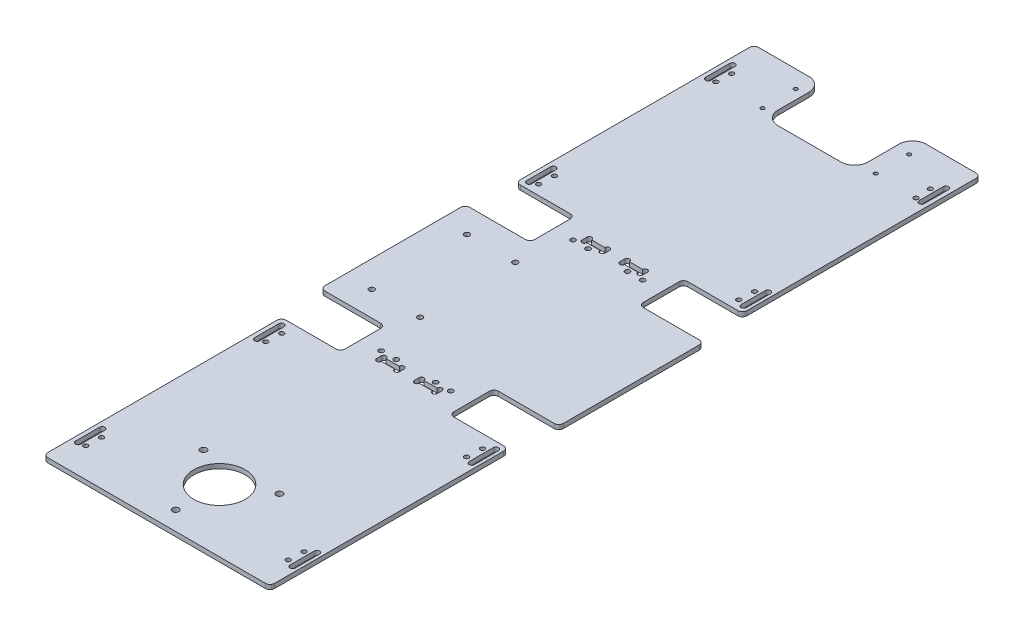
SolidWorks part; units mm, degrees
material "Thornel Mat VMA"
ref_plane "前视基准面" through (0, 0, 0) normal (0, 0, 1) x (1, 0, 0)
ref_plane "上视基准面" through (0, 0, 0) normal (0, 1, 0) x (1, 0, 0)
ref_plane "右视基准面" through (0, 0, 0) normal (1, 0, 0) x (0, 0, -1)
other "Configuration Table"
sketch "草图1" plane through (0, 0, 0) normal (0, 1, 0) x (1, 0, 0)
  line L0 (30.075, -69.59) -> (30.075, -66.41)
  line L1 (22.5, -69.59) -> (22.5, -66.41) construction
  line L7 (30.075, -68) -> (14.925, -68) construction
  line L8 (26.875, -69.59) -> (18.125, -69.59)
  line L9 (26.875, -66.41) -> (18.125, -66.41)
  line L14 (43.125, 69.59) -> (51.875, 69.59)
  line L15 (39.925, 69.59) -> (39.925, 66.41)
  line L16 (43.125, 66.41) -> (51.875, 66.41)
  line L17 (55.075, 69.59) -> (55.075, 66.41)
  line L18 (55.075, -69.59) -> (55.075, -66.41)
  line L19 (43.125, -66.41) -> (51.875, -66.41)
  line L20 (39.925, -69.59) -> (39.925, -66.41)
  line L21 (43.125, -69.59) -> (51.875, -69.59)
  line L22 (47.5, 69.59) -> (47.5, 66.41) construction
  line L23 (39.925, 68) -> (55.075, 68) construction
  line L24 (39.925, -68) -> (55.075, -68) construction
  line L25 (47.5, -69.59) -> (47.5, -66.41) construction
  line L27 (14.925, -69.59) -> (14.925, -66.41)
  line L29 (-1, -77.5) -> (-40, -77.5)
  line L30 (30.075, 68) -> (14.925, 68) construction
  line L31 (22.5, 69.59) -> (22.5, 66.41) construction
  line L33 (-1, 77.5) -> (-40, 77.5)
  line L54 (71, 77.5) -> (110, 77.5)
  line L56 (35, 153.4687) -> (35, -164.7089) construction
  line L58 (71, -77.5) -> (110, -77.5)
  line L64 (110, 235.15) -> (110, 77.5)
  line L67 (14.925, 69.59) -> (14.925, 66.41)
  line L68 (26.875, 66.41) -> (18.125, 66.41)
  line L69 (26.875, 69.59) -> (18.125, 69.59)
  line L70 (30.075, 69.59) -> (30.075, 66.41)
  line L72 (-40, 235.15) -> (110, 235.15)
  line L74 (-40, -235.15) -> (110, -235.15)
  line L77 (71, 77.5) -> (71, 47.9372)
  line L78 (-1, 77.5) -> (-1, 47.9372)
  line L84 (-40, 235.15) -> (-40, 77.5)
  line L85 (-1, 47.9372) -> (-43.8991, 47.9372)
  line L86 (-43.8991, 47.9372) -> (-43.8991, -47.9372)
  line L90 (113.8991, 47.9372) -> (113.8991, -47.9372)
  line L91 (71, 47.9372) -> (113.8991, 47.9372)
  line L93 (71, -47.9372) -> (113.8991, -47.9372)
  line L94 (-1, -47.9372) -> (-43.8991, -47.9372)
  line L95 (110, -77.5) -> (110, -235.15)
  line L96 (-1, -47.9372) -> (-1, -77.5)
  line L97 (71, -47.9372) -> (71, -77.5)
  line L98 (-40, -77.5) -> (-40, -235.15)
  arc A8 (39.925, 69.59) -> (43.125, 69.59) centre (41.525, 69.59) cw
  arc A9 (55.075, 69.59) -> (51.875, 69.59) centre (53.475, 69.59) ccw
  arc A10 (55.075, 66.41) -> (51.875, 66.41) centre (53.475, 66.41) cw
  arc A11 (39.925, 66.41) -> (43.125, 66.41) centre (41.525, 66.41) ccw
  arc A12 (39.925, -66.41) -> (43.125, -66.41) centre (41.525, -66.41) cw
  arc A13 (55.075, -66.41) -> (51.875, -66.41) centre (53.475, -66.41) ccw
  arc A14 (55.075, -69.59) -> (51.875, -69.59) centre (53.475, -69.59) cw
  arc A15 (39.925, -69.59) -> (43.125, -69.59) centre (41.525, -69.59) ccw
  circle A50 centre (48.025, -63.59) radius 1.6
  circle A51 centre (58.025, -63.59) radius 1.6
  circle A52 centre (58.025, 63.41) radius 1.6
  circle A53 centre (48.025, 63.41) radius 1.6
  arc A54 (30.075, -69.59) -> (26.875, -69.59) centre (28.475, -69.59) cw
  arc A55 (30.075, -66.41) -> (26.875, -66.41) centre (28.475, -66.41) ccw
  circle A56 centre (11.975, -63.59) radius 1.6
  circle A57 centre (21.975, -63.59) radius 1.6
  arc A58 (14.925, -69.59) -> (18.125, -69.59) centre (16.525, -69.59) ccw
  arc A59 (14.925, -66.41) -> (18.125, -66.41) centre (16.525, -66.41) cw
  circle A60 centre (21.975, 63.41) radius 1.6
  circle A61 centre (11.975, 63.41) radius 1.6
  arc A62 (30.075, 66.41) -> (26.875, 66.41) centre (28.475, 66.41) cw
  arc A63 (14.925, 66.41) -> (18.125, 66.41) centre (16.525, 66.41) ccw
  arc A64 (14.925, 69.59) -> (18.125, 69.59) centre (16.525, 69.59) cw
  arc A65 (30.075, 69.59) -> (26.875, 69.59) centre (28.475, 69.59) ccw
  point P28 (35, -97.5)
  point P79 (35, 97.5)
  point P141 (64, 0)
  point P146 (-64, 0)
  dimension "D12" = 4.925
extrude "凸台-拉伸1" add sketch "草图1" along normal blind 3
fillet "圆角1" radius 3 20 edges at (-40, 1.5, -235.15) (110, 1.5, -235.15) (113.8991, 1.5, -47.9372) (110, 1.5, -77.5) (71, 1.5, -77.5) (71, 1.5, -47.9372) (-40, 1.5, -77.5) (-1, 1.5, -77.5) (-1, 1.5, -47.9372) (-43.8991, 1.5, -47.9372) (-43.8991, 1.5, 47.9372) (-1, 1.5, 47.9372) (113.8991, 1.5, 47.9372) (71, 1.5, 47.9372) (-40, 1.5, 77.5) (-1, 1.5, 77.5) (71, 1.5, 77.5) (110, 1.5, 77.5) (110, 1.5, 235.15) (-40, 1.5, 235.15)
sketch "草图2" plane through (0, 3, 0) normal (0, 1, 0) x (1, 0, 0)
  line L0 (107.85, 215.4743) -> (104.85, 215.4743) construction
  line L1 (107.85, 216.4743) -> (104.85, 216.4743)
  line L2 (107.85, 216.4743) -> (107.85, 200.4743)
  line L3 (107.85, 200.4743) -> (104.85, 200.4743)
  line L4 (104.85, 216.4743) -> (104.85, 200.4743)
  line L5 (107.85, 98) -> (104.85, 98)
  line L6 (107.85, 98) -> (107.85, 82)
  line L7 (107.85, 82) -> (104.85, 82)
  line L8 (104.85, 98) -> (104.85, 82)
  line L9 (-34.15, 216.4743) -> (-37.15, 216.4743)
  line L10 (-34.15, 216.4743) -> (-34.15, 200.4743)
  line L11 (-34.15, 200.4743) -> (-37.15, 200.4743)
  line L12 (-37.15, 216.4743) -> (-37.15, 200.4743)
  line L13 (-34.15, 98) -> (-37.15, 98)
  line L14 (-34.15, 98) -> (-34.15, 82)
  line L15 (-34.15, 82) -> (-37.15, 82)
  line L16 (-37.15, 98) -> (-37.15, 82)
  line L17 (107.85, 214.4743) -> (104.85, 214.4743)
  line L18 (107.85, 216.4743) -> (104.85, 216.4743)
  line L19 (107.85, 201.4743) -> (104.85, 201.4743) construction
  line L20 (107.85, 200.4743) -> (104.85, 200.4743)
  line L21 (107.85, 202.4743) -> (104.85, 202.4743)
  line L22 (107.85, 97) -> (104.85, 97) construction
  line L23 (107.85, 96) -> (104.85, 96)
  line L24 (107.85, 98) -> (104.85, 98)
  line L25 (107.85, 83) -> (104.85, 83) construction
  line L26 (107.85, 82) -> (104.85, 82)
  line L27 (107.85, 84) -> (104.85, 84)
  line L28 (-34.15, 215.4743) -> (-37.15, 215.4743) construction
  line L29 (-34.15, 214.4743) -> (-37.15, 214.4743)
  line L30 (-34.15, 216.4743) -> (-37.15, 216.4743)
  line L31 (-34.15, 201.4743) -> (-37.15, 201.4743) construction
  line L32 (-34.15, 200.4743) -> (-37.15, 200.4743)
  line L33 (-34.15, 202.4743) -> (-37.15, 202.4743)
  line L34 (-34.15, 97) -> (-37.15, 97) construction
  line L35 (-34.15, 96) -> (-37.15, 96)
  line L36 (-34.15, 98) -> (-37.15, 98)
  line L37 (-34.15, 83) -> (-37.15, 83) construction
  line L38 (-34.15, 82) -> (-37.15, 82)
  line L39 (-34.15, 84) -> (-37.15, 84)
  line L40 (107.85, 208.4743) -> (96.4125, 208.4743) construction
  line L41 (107.85, 90) -> (95.3231, 90) construction
  line L42 (-37.15, 90) -> (-24.8235, 90) construction
  line L43 (-37.15, 208.4743) -> (-26.5733, 208.4743) construction
  arc A0 (107.85, 214.4743) -> (107.85, 216.4743) centre (107.85, 215.4743) ccw
  arc A1 (104.85, 216.4743) -> (104.85, 214.4743) centre (104.85, 215.4743) ccw
  arc A2 (107.85, 200.4743) -> (107.85, 202.4743) centre (107.85, 201.4743) ccw
  arc A3 (104.85, 202.4743) -> (104.85, 200.4743) centre (104.85, 201.4743) ccw
  arc A4 (107.85, 96) -> (107.85, 98) centre (107.85, 97) ccw
  arc A5 (104.85, 98) -> (104.85, 96) centre (104.85, 97) ccw
  arc A6 (107.85, 82) -> (107.85, 84) centre (107.85, 83) ccw
  arc A7 (104.85, 84) -> (104.85, 82) centre (104.85, 83) ccw
  arc A8 (-34.15, 214.4743) -> (-34.15, 216.4743) centre (-34.15, 215.4743) ccw
  arc A9 (-37.15, 216.4743) -> (-37.15, 214.4743) centre (-37.15, 215.4743) ccw
  arc A10 (-34.15, 200.4743) -> (-34.15, 202.4743) centre (-34.15, 201.4743) ccw
  arc A11 (-37.15, 202.4743) -> (-37.15, 200.4743) centre (-37.15, 201.4743) ccw
  arc A12 (-34.15, 96) -> (-34.15, 98) centre (-34.15, 97) ccw
  arc A13 (-37.15, 98) -> (-37.15, 96) centre (-37.15, 97) ccw
  arc A14 (-34.15, 82) -> (-34.15, 84) centre (-34.15, 83) ccw
  arc A15 (-37.15, 84) -> (-37.15, 82) centre (-37.15, 83) ccw
  circle A16 centre (101.35, 203.4743) radius 1.5
  circle A17 centre (101.35, 213.4743) radius 1.5
  circle A18 centre (101.35, 85) radius 1.5
  circle A19 centre (101.35, 95) radius 1.5
  circle A20 centre (-30.65, 95) radius 1.5
  circle A21 centre (-30.65, 85) radius 1.5
  circle A22 centre (-30.65, 213.4743) radius 1.5
  circle A23 centre (-30.65, 203.4743) radius 1.5
  point P26 (106.35, 215.4743)
  point P31 (106.35, 201.4743)
  point P38 (106.35, 97)
  point P45 (106.35, 83)
  point P52 (-35.65, 215.4743)
  point P59 (-35.65, 201.4743)
  point P66 (-35.65, 97)
  point P73 (-35.65, 83)
  dimension "D1" = 1
  dimension "D2" = 1
  dimension "D3" = 1
  dimension "D4" = 1
  dimension "D5" = 1
  dimension "D6" = 1
  dimension "D7" = 1
  dimension "D8" = 1
  dimension "D9" = 3
  dimension "D14" = 3
  dimension "D15" = 3
  dimension "D18" = 3
  dimension "D10" = 3.5
  dimension "D11" = 5
  dimension "D12" = 3.5
  dimension "D13" = 5
  dimension "D16" = 3.5
  dimension "D17" = 5
  dimension "D19" = 5
  dimension "D20" = 3.5
sketch "草图3" plane through (0, 3, 0) normal (0, 1, 0) x (1, 0, 0)
  line L2 (104.85, 214.4743) -> (107.85, 214.4743)
  line L3 (107.85, 216.4743) -> (104.85, 216.4743)
  line L4 (-34.15, 216.4743) -> (-37.15, 216.4743)
  line L5 (-37.15, 216.4743) -> (-37.15, 200.4743)
  line L6 (-37.15, 200.4743) -> (-34.15, 200.4743)
  line L7 (-34.15, 200.4743) -> (-34.15, 216.4743)
  line L8 (-34.15, 216.4743) -> (-37.15, 216.4743)
  line L9 (-37.15, 216.4743) -> (-37.15, 200.4743)
  line L10 (-37.15, 200.4743) -> (-34.15, 200.4743)
  line L11 (-34.15, 200.4743) -> (-34.15, 216.4743)
  line L12 (107.85, 98) -> (104.85, 98)
  line L13 (104.85, 98) -> (104.85, 82)
  line L14 (104.85, 82) -> (107.85, 82)
  line L15 (107.85, 82) -> (107.85, 98)
  line L16 (107.85, 98) -> (104.85, 98)
  line L17 (104.85, 98) -> (104.85, 82)
  line L18 (104.85, 82) -> (107.85, 82)
  line L19 (107.85, 82) -> (107.85, 98)
  line L20 (107.85, 216.4743) -> (104.85, 216.4743)
  line L21 (104.85, 216.4743) -> (104.85, 200.4743)
  line L22 (104.85, 200.4743) -> (107.85, 200.4743)
  line L23 (107.85, 200.4743) -> (107.85, 216.4743)
  line L24 (107.85, 216.4743) -> (104.85, 216.4743)
  line L25 (104.85, 216.4743) -> (104.85, 200.4743)
  line L26 (104.85, 200.4743) -> (107.85, 200.4743)
  line L27 (107.85, 200.4743) -> (107.85, 216.4743)
  line L28 (104.85, 214.4743) -> (107.85, 214.4743)
  line L29 (107.85, 216.4743) -> (104.85, 216.4743)
  line L30 (104.85, 96) -> (107.85, 96)
  line L31 (107.85, 98) -> (104.85, 98)
  line L32 (-34.15, 98) -> (-37.15, 98)
  line L33 (-37.15, 98) -> (-37.15, 82)
  line L34 (-37.15, 82) -> (-34.15, 82)
  line L35 (-34.15, 82) -> (-34.15, 98)
  line L36 (-34.15, 98) -> (-37.15, 98)
  line L37 (-37.15, 98) -> (-37.15, 82)
  line L38 (-37.15, 82) -> (-34.15, 82)
  line L39 (-34.15, 82) -> (-34.15, 98)
  line L40 (104.85, 96) -> (107.85, 96)
  line L41 (107.85, 98) -> (104.85, 98)
  line L42 (104.85, 200.4743) -> (107.85, 200.4743)
  line L43 (107.85, 202.4743) -> (104.85, 202.4743)
  line L44 (104.85, 200.4743) -> (107.85, 200.4743)
  line L45 (107.85, 202.4743) -> (104.85, 202.4743)
  line L46 (-37.15, 214.4743) -> (-34.15, 214.4743)
  line L47 (-34.15, 216.4743) -> (-37.15, 216.4743)
  line L48 (-37.15, 214.4743) -> (-34.15, 214.4743)
  line L49 (-34.15, 216.4743) -> (-37.15, 216.4743)
  line L50 (104.85, 82) -> (107.85, 82)
  line L51 (107.85, 84) -> (104.85, 84)
  line L52 (104.85, 82) -> (107.85, 82)
  line L53 (107.85, 84) -> (104.85, 84)
  line L54 (-37.15, 82) -> (-34.15, 82)
  line L55 (-34.15, 84) -> (-37.15, 84)
  line L56 (-37.15, 82) -> (-34.15, 82)
  line L57 (-34.15, 84) -> (-37.15, 84)
  line L58 (-37.15, 96) -> (-34.15, 96)
  line L59 (-34.15, 98) -> (-37.15, 98)
  line L60 (-37.15, 96) -> (-34.15, 96)
  line L61 (-34.15, 98) -> (-37.15, 98)
  line L67 (-37.15, -200.4743) -> (-34.15, -200.4743)
  line L68 (-35.15, -202.8885) -> (-37.15, -202.4743)
  line L69 (-34.15, -98) -> (-37.15, -98)
  line L70 (-37.15, -96) -> (-34.15, -96)
  line L71 (-34.15, -84) -> (-37.15, -84)
  line L72 (-37.15, -82) -> (-34.15, -82)
  line L73 (107.85, -84) -> (104.85, -84)
  line L74 (104.85, -82) -> (107.85, -82)
  line L75 (-34.15, -216.4743) -> (-37.15, -216.4743)
  line L76 (-37.15, -214.4743) -> (-34.15, -214.4743)
  line L77 (107.85, -202.4743) -> (104.85, -202.4743)
  line L78 (104.85, -200.4743) -> (107.85, -200.4743)
  line L79 (107.85, -98) -> (104.85, -98)
  line L80 (104.85, -96) -> (107.85, -96)
  line L81 (-34.15, -82) -> (-34.15, -98)
  line L82 (-37.15, -82) -> (-34.15, -82)
  line L83 (-37.15, -98) -> (-37.15, -82)
  line L84 (-34.15, -98) -> (-37.15, -98)
  line L85 (107.85, -216.4743) -> (104.85, -216.4743)
  line L86 (104.85, -214.4743) -> (107.85, -214.4743)
  line L87 (107.85, -200.4743) -> (107.85, -216.4743)
  line L88 (104.85, -200.4743) -> (107.85, -200.4743)
  line L89 (104.85, -216.4743) -> (104.85, -200.4743)
  line L90 (107.85, -216.4743) -> (104.85, -216.4743)
  line L91 (107.85, -82) -> (107.85, -98)
  line L92 (104.85, -82) -> (107.85, -82)
  line L93 (104.85, -98) -> (104.85, -82)
  line L94 (107.85, -98) -> (104.85, -98)
  line L95 (-34.15, -200.4743) -> (-34.15, -216.4743)
  line L96 (-37.15, -200.4743) -> (-34.15, -200.4743)
  line L97 (-37.15, -216.4743) -> (-37.15, -200.4743)
  line L98 (-34.15, -216.4743) -> (-37.15, -216.4743)
  line L99 (-35.65, 216.4743) -> (-35.65, 200.4743) construction
  line L100 (-33.8992, 216.4743) -> (-33.8992, 200.4743)
  line L101 (-37.4008, 216.4743) -> (-37.4008, 200.4743)
  line L104 (105.65, 216.4743) -> (105.65, 200.4743) construction
  line L105 (103.8992, 216.4743) -> (103.8992, 200.4743)
  line L106 (107.4008, 216.4743) -> (107.4008, 200.4743)
  circle A0 centre (-30.65, -85) radius 1.5
  circle A1 centre (-30.65, 95) radius 1.5
  arc A2 (104.85, 216.4743) -> (104.85, 214.4743) centre (104.85, 215.4743) ccw
  arc A3 (107.85, 214.4743) -> (107.85, 216.4743) centre (107.85, 215.4743) ccw
  arc A4 (104.85, 216.4743) -> (104.85, 214.4743) centre (104.85, 215.4743) ccw
  arc A5 (107.85, 214.4743) -> (107.85, 216.4743) centre (107.85, 215.4743) ccw
  arc A6 (104.85, 98) -> (104.85, 96) centre (104.85, 97) ccw
  arc A7 (107.85, 96) -> (107.85, 98) centre (107.85, 97) ccw
  arc A8 (104.85, 98) -> (104.85, 96) centre (104.85, 97) ccw
  arc A9 (107.85, 96) -> (107.85, 98) centre (107.85, 97) ccw
  arc A10 (104.85, 202.4743) -> (104.85, 200.4743) centre (104.85, 201.4743) ccw
  arc A11 (107.85, 200.4743) -> (107.85, 202.4743) centre (107.85, 201.4743) ccw
  arc A12 (104.85, 202.4743) -> (104.85, 200.4743) centre (104.85, 201.4743) ccw
  arc A13 (107.85, 200.4743) -> (107.85, 202.4743) centre (107.85, 201.4743) ccw
  arc A14 (-37.15, 216.4743) -> (-37.15, 214.4743) centre (-37.15, 215.4743) ccw
  arc A15 (-34.15, 214.4743) -> (-34.15, 216.4743) centre (-34.15, 215.4743) ccw
  arc A16 (-37.15, 216.4743) -> (-37.15, 214.4743) centre (-37.15, 215.4743) ccw
  arc A18 (104.85, 84) -> (104.85, 82) centre (104.85, 83) ccw
  arc A19 (107.85, 82) -> (107.85, 84) centre (107.85, 83) ccw
  arc A20 (104.85, 84) -> (104.85, 82) centre (104.85, 83) ccw
  arc A21 (107.85, 82) -> (107.85, 84) centre (107.85, 83) ccw
  arc A22 (-37.15, 84) -> (-37.15, 82) centre (-37.15, 83) ccw
  arc A23 (-34.15, 82) -> (-34.15, 84) centre (-34.15, 83) ccw
  arc A24 (-37.15, 84) -> (-37.15, 82) centre (-37.15, 83) ccw
  arc A25 (-34.15, 82) -> (-34.15, 84) centre (-34.15, 83) ccw
  arc A26 (-37.15, 98) -> (-37.15, 96) centre (-37.15, 97) ccw
  arc A27 (-34.15, 96) -> (-34.15, 98) centre (-34.15, 97) ccw
  arc A28 (-37.15, 98) -> (-37.15, 96) centre (-37.15, 97) ccw
  arc A29 (-34.15, 96) -> (-34.15, 98) centre (-34.15, 97) ccw
  circle A34 centre (-30.65, 95) radius 1.5
  circle A35 centre (101.35, 95) radius 1.5
  circle A36 centre (101.35, 95) radius 1.5
  circle A37 centre (101.35, 85) radius 1.5
  circle A38 centre (101.35, 85) radius 1.5
  circle A39 centre (101.35, 213.4743) radius 1.5
  circle A40 centre (101.35, 213.4743) radius 1.5
  circle A41 centre (101.35, 203.4743) radius 1.5
  circle A42 centre (101.35, 203.4743) radius 1.5
  circle A43 centre (-30.65, 203.4743) radius 1.5
  circle A44 centre (-30.65, 203.4743) radius 1.5
  circle A45 centre (-30.65, 213.4743) radius 1.5
  circle A46 centre (-30.65, 213.4743) radius 1.5
  circle A47 centre (-30.65, 85) radius 1.5
  circle A48 centre (-30.65, 85) radius 1.5
  circle A49 centre (-30.65, -213.4743) radius 1.5
  circle A50 centre (-30.65, -203.4743) radius 1.5
  circle A51 centre (101.35, -203.4743) radius 1.5
  circle A52 centre (101.35, -213.4743) radius 1.5
  circle A53 centre (101.35, -85) radius 1.5
  circle A54 centre (101.35, -95) radius 1.5
  circle A55 centre (-30.65, -95) radius 1.5
  arc A56 (-34.15, -200.4743) -> (-35.15, -202.8885) centre (-35.15, -201.4743) cw
  arc A57 (-37.15, -202.4743) -> (-37.15, -200.4743) centre (-37.15, -201.4743) cw
  arc A58 (-34.15, -96) -> (-34.15, -98) centre (-34.15, -97) cw
  arc A59 (-37.15, -98) -> (-37.15, -96) centre (-37.15, -97) cw
  arc A60 (-34.15, -82) -> (-34.15, -84) centre (-34.15, -83) cw
  arc A61 (-37.15, -84) -> (-37.15, -82) centre (-37.15, -83) cw
  arc A62 (107.85, -82) -> (107.85, -84) centre (107.85, -83) cw
  arc A63 (104.85, -84) -> (104.85, -82) centre (104.85, -83) cw
  arc A64 (-34.15, -214.4743) -> (-34.15, -216.4743) centre (-34.15, -215.4743) cw
  arc A65 (-37.15, -216.4743) -> (-37.15, -214.4743) centre (-37.15, -215.4743) cw
  arc A66 (107.85, -200.4743) -> (107.85, -202.4743) centre (107.85, -201.4743) cw
  arc A67 (104.85, -202.4743) -> (104.85, -200.4743) centre (104.85, -201.4743) cw
  arc A68 (107.85, -96) -> (107.85, -98) centre (107.85, -97) cw
  arc A69 (104.85, -98) -> (104.85, -96) centre (104.85, -97) cw
  arc A70 (107.85, -214.4743) -> (107.85, -216.4743) centre (107.85, -215.4743) cw
  arc A71 (104.85, -216.4743) -> (104.85, -214.4743) centre (104.85, -215.4743) cw
  arc A72 (-33.8992, 216.4743) -> (-37.4008, 216.4743) centre (-35.65, 216.4743) ccw
  arc A73 (-37.4008, 200.4743) -> (-33.8992, 200.4743) centre (-35.65, 200.4743) ccw
  arc A74 (103.8992, 216.4743) -> (107.4008, 216.4743) centre (105.65, 216.4743) cw
  arc A75 (107.4008, 200.4743) -> (103.8992, 200.4743) centre (105.65, 200.4743) cw
  point P61 (-35.65, 208.4743)
  point P165 (105.65, 208.4743)
  dimension "D12" = 3.5016
  dimension "D1" = 0
  dimension "D2" = 0
  dimension "D3" = 0
  dimension "D4" = 0
  dimension "D5" = 0
  dimension "D6" = 0
  dimension "D7" = 0
  dimension "D8" = 0
  dimension "D9" = 0
  dimension "D10" = 0
  dimension "D11" = 0
  dimension "D13" = 0
  dimension "D14" = 0
  dimension "D15" = 0
  dimension "D16" = 0
  dimension "D17" = 0
  dimension "D18" = 0
  dimension "D19" = 0
  dimension "D20" = 0
extrude "切除-拉伸3" cut sketch "草图3<4>" against normal through all contours L100 A73 L101 A72
sketch "草图3<4>" plane through (0, 3, 0) normal (0, 1, 0) x (1, 0, 0) same geometry as "草图3"
extrude "切除-拉伸4" cut sketch "草图3" against normal through all contours L106 A75 L105 A74
sketch "草图4" plane through (0, 3, 0) normal (0, 1, 0) x (1, 0, 0)
  line L0 (-35.65, 98) -> (-35.65, 82) construction
  line L1 (-34.15, 98) -> (-37.15, 98) construction
  line L2 (-37.15, 82) -> (-34.15, 82) construction
  line L3 (-33.9, 98) -> (-33.9, 82)
  line L4 (-37.4, 98) -> (-37.4, 82)
  line L5 (106.35, 98) -> (106.35, 82) construction
  line L6 (107.85, 98) -> (104.85, 98) construction
  line L7 (104.85, 82) -> (107.85, 82) construction
  line L8 (108.1, 98) -> (108.1, 82)
  line L9 (104.6, 98) -> (104.6, 82)
  line L10 (-35.65, -82) -> (-35.65, -98) construction
  line L11 (-37.15, -82) -> (-34.15, -82) construction
  line L12 (-34.15, -98) -> (-37.15, -98) construction
  line L13 (-33.9, -82) -> (-33.9, -98)
  line L14 (-37.4, -82) -> (-37.4, -98)
  line L15 (106.35, -82) -> (106.35, -98) construction
  line L16 (104.85, -82) -> (107.85, -82) construction
  line L17 (107.85, -98) -> (104.85, -98) construction
  line L18 (108.1, -82) -> (108.1, -98)
  line L19 (104.6, -82) -> (104.6, -98)
  line L20 (-35.65, -200.4743) -> (-35.65, -216.4743) construction
  line L21 (-37.15, -200.4743) -> (-34.15, -200.4743) construction
  line L22 (-34.15, -216.4743) -> (-37.15, -216.4743) construction
  line L23 (-33.9, -200.4743) -> (-33.9, -216.4743)
  line L24 (-37.4, -200.4743) -> (-37.4, -216.4743)
  line L25 (106.35, -200.4743) -> (106.35, -216.4743) construction
  line L26 (104.85, -200.4743) -> (107.85, -200.4743) construction
  line L27 (107.85, -216.4743) -> (104.85, -216.4743) construction
  line L28 (108.1, -200.4743) -> (108.1, -216.4743)
  line L29 (104.6, -200.4743) -> (104.6, -216.4743)
  arc A0 (-33.9, 98) -> (-37.4, 98) centre (-35.65, 98) ccw
  arc A1 (-37.4, 82) -> (-33.9, 82) centre (-35.65, 82) ccw
  arc A2 (108.1, 98) -> (104.6, 98) centre (106.35, 98) ccw
  arc A3 (104.6, 82) -> (108.1, 82) centre (106.35, 82) ccw
  arc A4 (-33.9, -82) -> (-37.4, -82) centre (-35.65, -82) ccw
  arc A5 (-37.4, -98) -> (-33.9, -98) centre (-35.65, -98) ccw
  arc A6 (108.1, -82) -> (104.6, -82) centre (106.35, -82) ccw
  arc A7 (104.6, -98) -> (108.1, -98) centre (106.35, -98) ccw
  arc A8 (-33.9, -200.4743) -> (-37.4, -200.4743) centre (-35.65, -200.4743) ccw
  arc A9 (-37.4, -216.4743) -> (-33.9, -216.4743) centre (-35.65, -216.4743) ccw
  arc A10 (108.1, -200.4743) -> (104.6, -200.4743) centre (106.35, -200.4743) ccw
  arc A11 (104.6, -216.4743) -> (108.1, -216.4743) centre (106.35, -216.4743) ccw
  point P6 (-35.65, 90)
  point P11 (106.35, 90)
  point P22 (-35.65, -90)
  point P33 (106.35, -90)
  point P44 (-35.65, -208.4743)
  point P55 (106.35, -208.4743)
  dimension "D1" = 3.5
  dimension "D2" = 3.5
  dimension "D3" = 3.5
  dimension "D4" = 3.5
  dimension "D5" = 3.5
  dimension "D6" = 3.5
extrude "切除-拉伸5" cut sketch "草图4" against normal through all contours L4 A1 L3 A0 | L8 A3 L9 A2 | L18 A7 L19 A6 | L28 A11 L29 A10 | L23 A9 L24 A8 | L13 A5 L14 A4 region at (-35.65, 3, -90)
sketch "草图5" plane through (0, 3, 0) normal (0, 1, 0) x (1, 0, 0)
  line L0 (-33.8992, 216.4743) -> (-33.8992, 200.4743) construction
  line L1 (103.8992, 216.4743) -> (103.8992, 200.4743) construction
  line L2 (104.6, 98) -> (104.6, 82) construction
  line L3 (-33.9, 98) -> (-33.9, 82) construction
  line L4 (-33.9, -82) -> (-33.9, -98) construction
  line L5 (104.6, -82) -> (104.6, -98) construction
  line L6 (-33.9, -200.4743) -> (-33.9, -216.4743) construction
  line L7 (104.6, -200.4743) -> (104.6, -216.4743) construction
  circle A0 centre (-30.8992, 211.2264) radius 1.5
  circle A1 centre (-31.3986, 201.2389) radius 1.5
  circle A2 centre (100.8992, 210.9587) radius 1.5
  circle A3 centre (101.3986, 200.9712) radius 1.5
  circle A4 centre (101.6, 93.9705) radius 1.5
  circle A5 centre (101.1006, 83.983) radius 1.5
  circle A6 centre (-30.9, 93.9705) radius 1.5
  circle A7 centre (-31.3994, 83.983) radius 1.5
  circle A8 centre (-30.9, -86.5689) radius 1.5
  circle A9 centre (-31.3994, -96.5564) radius 1.5
  circle A10 centre (101.6, -86.1482) radius 1.5
  circle A11 centre (101.1006, -96.1357) radius 1.5
  circle A12 centre (-30.9, -205.7402) radius 1.5
  circle A13 centre (-31.3994, -215.7277) radius 1.5
  circle A14 centre (101.6, -204.2499) radius 1.5
  circle A15 centre (101.1006, -214.2374) radius 1.5
  dimension "D3" = 3
  dimension "D4" = 3
  dimension "D6" = 3
  dimension "D7" = 3
  dimension "D10" = 3
  dimension "D11" = 3
  dimension "D12" = 3
  dimension "D13" = 3
  dimension "D14" = 3
  dimension "D17" = 3
  dimension "D18" = 3
  dimension "D21" = 3
  dimension "D22" = 3
  dimension "D25" = 3
  dimension "D26" = 3
  dimension "D29" = 3
  dimension "D30" = 3
  dimension "D1" = 10
  dimension "D2" = 3
  dimension "D5" = 10
  dimension "D8" = 3
  dimension "D9" = 10
  dimension "D15" = 10
  dimension "D16" = 3
  dimension "D19" = 10
  dimension "D20" = 3
  dimension "D23" = 10
  dimension "D24" = 3
  dimension "D27" = 10
  dimension "D28" = 3
  dimension "D31" = 10
  dimension "D32" = 3
extrude "切除-拉伸6" cut sketch "草图5" against normal through all contours A14 | A15 | A13 | A12 | A8 | A9 | A10 | A2 | A3 | A4 | A5 | A0 | A1 | A2 | A3 | A7 | A6 | A4 | A5 | A8 | A9 | A10 region at (100.8992, 3, -210.9587) region at (101.3986, 3, -200.9712) region at (101.6, 3, -93.9705) region at (101.1006, 3, -83.983) region at (-30.9, 3, 86.5689) region at (-31.3994, 3, 96.5564) region at (101.6, 3, 86.1482) region at (-30.9, 3, 205.7402) region at (-31.3994, 3, 215.7277) region at (101.6, 3, 204.2499) region at (101.1006, 3, 214.2374)
sketch "草图7" plane through (0, 3, 0) normal (0, 1, 0) x (1, 0, 0)
  circle A0 centre (101.1, -96.1482) radius 1.5
extrude "切除-拉伸7" cut sketch "草图7" against normal through all
sketch "草图9" plane through (0, 3, 0) normal (0, 1, 0) x (1, 0, 0)
  arc A8 (49.8676, -202.2048) -> (20.4228, -185.2048) centre (35.1452, -193.7048) ccw
  arc A9 (20.4228, -185.2048) -> (49.8676, -202.2048) centre (35.1452, -193.7048) ccw
  arc A10 (8.2118, -178.1548) -> (11.8491, -180.2548) centre (10.0305, -179.2048) ccw
  arc A11 (11.8491, -180.2548) -> (8.2118, -178.1548) centre (10.0305, -179.2048) ccw
  arc A12 (58.4413, -178.1548) -> (62.0786, -180.2548) centre (60.26, -179.2048) ccw
  arc A13 (62.0786, -180.2548) -> (58.4413, -178.1548) centre (60.26, -179.2048) ccw
  arc A14 (33.3266, -221.6548) -> (36.9639, -223.7548) centre (35.1452, -222.7048) ccw
  arc A15 (36.9639, -223.7548) -> (33.3266, -221.6548) centre (35.1452, -222.7048) ccw
  dimension "D1" = 17
extrude "切除-拉伸8" cut sketch "草图9" against normal blind 10
sketch "草图10" plane through (0, 3, 0) normal (0, 1, 0) x (1, 0, 0)
  line L0 (64.9021, 235.15) -> (64.9021, 196.7413)
  line L1 (107, 235.15) -> (-37, 235.15) construction
  line L2 (64.9021, 196.7413) -> (5.3462, 196.7413)
  line L3 (5.3462, 196.7413) -> (5.3462, 235.15)
  line L4 (5.3462, 235.15) -> (64.9021, 235.15)
extrude "切除-拉伸9" cut sketch "草图10" against normal blind 10
sketch "草图12" plane through (0, 3, 0) normal (0, 1, 0) x (1, 0, 0)
  arc A8 (-2.142, 201.65) -> (0.358, 201.65) centre (-0.892, 201.65) ccw
  arc A9 (0.358, 201.65) -> (-2.142, 201.65) centre (-0.892, 201.65) ccw
  arc A10 (-2.142, 223.65) -> (0.358, 223.65) centre (-0.892, 223.65) ccw
  arc A11 (0.358, 223.65) -> (-2.142, 223.65) centre (-0.892, 223.65) ccw
  arc A12 (72.858, 201.65) -> (75.358, 201.65) centre (74.108, 201.65) ccw
  arc A13 (75.358, 201.65) -> (72.858, 201.65) centre (74.108, 201.65) ccw
  arc A14 (75.358, 223.65) -> (72.858, 223.65) centre (74.108, 223.65) ccw
  arc A15 (72.858, 223.65) -> (75.358, 223.65) centre (74.108, 223.65) ccw
extrude "切除-拉伸10" cut sketch "草图12" against normal blind 10
fillet "圆角2" radius 9 4 edges at (5.3462, 1.5, -235.15) (5.3462, 1.5, -196.7413) (64.9021, 1.5, -196.7413) (64.9021, 1.5, -235.15)
sketch "草图13" plane through (0, 0, 0) normal (0, -1, 0) x (1, 0, 0)
  line L0 (-71.1643, 0) -> (140.8838, 0) construction
  line L1 (-10.315, 61.4411) -> (-10.315, -56.2121) construction
  circle A1 centre (-26.315, 31.5) radius 1.75
  circle A2 centre (5.685, 31.5) radius 1.75
  circle A3 centre (-26.315, -31.5) radius 1.75
  circle A4 centre (5.685, -31.5) radius 1.75
  dimension "D1" = 3.5
  dimension "D2" = 32
  dimension "D3" = 63
extrude "切除-拉伸11" cut sketch "草图13" against normal blind 10
